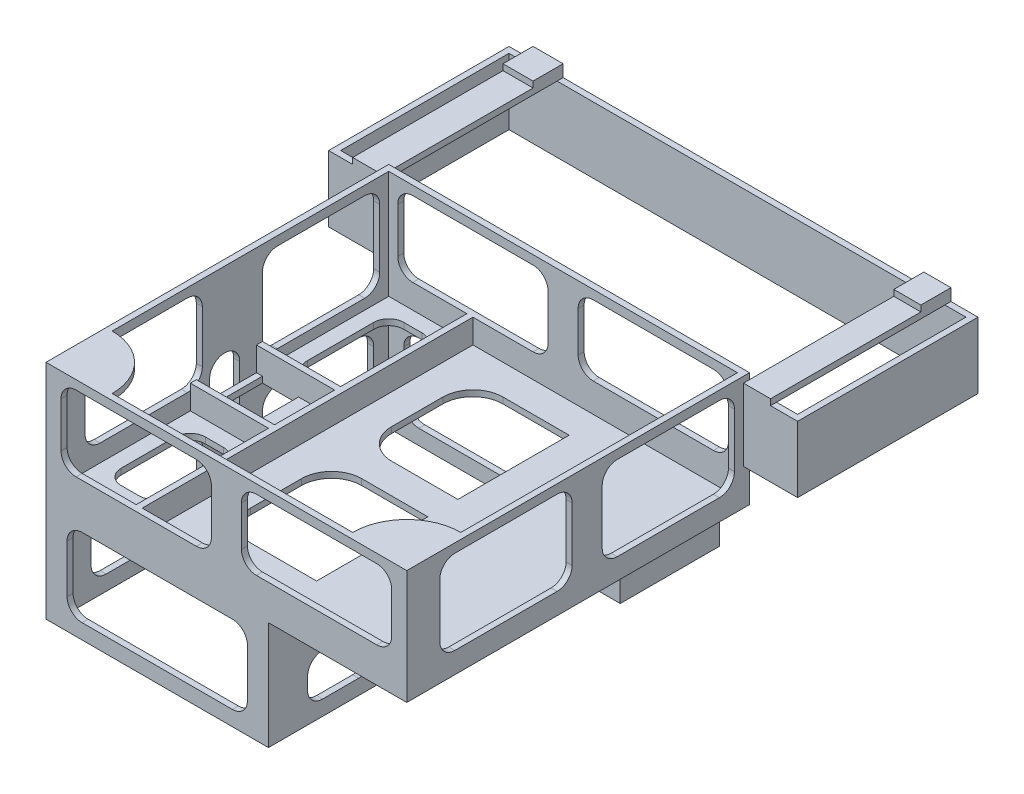
SolidWorks part; units mm, degrees
ref_plane "Front Plane" through (0, 0, 0) normal (0, 0, 1) x (1, 0, 0)
ref_plane "Top Plane" through (0, 0, 0) normal (0, 1, 0) x (1, 0, 0)
ref_plane "Right Plane" through (0, 0, 0) normal (1, 0, 0) x (0, 0, -1)
sketch "Sketch1" plane through (0, 0, 0) normal (0, 1, 0) x (1, 0, 0)
  line L1 (-113.8745, -60.9464) -> (-53.8745, -60.9464)
  line L2 (-113.8745, -60.9464) -> (-113.8745, -6.9464)
  line L3 (-113.8745, -6.9464) -> (-53.8745, -6.9464)
  line L4 (-53.8745, -60.9464) -> (-53.8745, -6.9464)
  dimension "D1" = 60
  dimension "D2" = 54
extrude "Boss-Extrude1" add sketch "Sketch1" along normal blind 38
sketch "Sketch2" plane through (0, 38, 0) normal (0, 1, 0) x (1, 0, 0)
  line L0 (-53.8745, -60.9464) -> (-53.8745, -6.9464) construction
  line L1 (-54.8745, -7.9464) -> (-98.8745, -7.9464)
  line L2 (-54.8745, -7.9464) -> (-54.8745, -59.9464)
  line L3 (-54.8745, -59.9464) -> (-98.8745, -59.9464)
  line L4 (-98.8745, -7.9464) -> (-98.8745, -59.9464)
  line L5 (-53.8745, -6.9464) -> (-113.8745, -6.9464) construction
  line L6 (-113.8745, -60.9464) -> (-53.8745, -60.9464) construction
  dimension "D1" = 1
  dimension "D2" = 1
  dimension "D3" = 1
  dimension "D4" = 44
extrude "Cut-Extrude1" cut sketch "Sketch2" against normal blind 19
sketch "Sketch3" plane through (0, 0, 0) normal (0, -1, 0) x (-1, 0, 0)
  line L0 (113.8745, -60.9464) -> (53.8745, -60.9464) construction
  line L1 (112.8745, -59.9464) -> (77.8745, -59.9464)
  line L2 (112.8745, -59.9464) -> (112.8745, -7.9464)
  line L3 (112.8745, -7.9464) -> (77.8745, -7.9464)
  line L4 (77.8745, -59.9464) -> (77.8745, -7.9464)
  line L5 (113.8745, -6.9464) -> (113.8745, -60.9464) construction
  line L6 (53.8745, -6.9464) -> (113.8745, -6.9464) construction
  dimension "D1" = 1
  dimension "D2" = 35
  dimension "D3" = 1
  dimension "D4" = 1
extrude "Cut-Extrude2" cut sketch "Sketch3" against normal blind 18
sketch "Sketch4" plane through (0, 18, 0) normal (0, -1, 0) x (-1, 0, 0)
  line L0 (77.8745, -59.9464) -> (112.8745, -59.9464) construction
  line L1 (111.8745, -39.9464) -> (105.8745, -39.9464)
  line L2 (111.8745, -39.9464) -> (111.8745, -29.9464)
  line L3 (111.8745, -29.9464) -> (105.8745, -29.9464)
  line L4 (105.8745, -39.9464) -> (105.8745, -29.9464)
  line L5 (112.8745, -7.9464) -> (77.8745, -7.9464) construction
  line L6 (112.8745, -59.9464) -> (112.8745, -7.9464) construction
  dimension "D1" = 20
  dimension "D2" = 22
  dimension "D3" = 1
  dimension "D4" = 6
extrude "Cut-Extrude3" cut sketch "Sketch4" against normal blind 38
sketch "Sketch5" plane through (0, 38, 0) normal (0, 1, 0) x (1, 0, 0)
  line L0 (-53.8745, -6.9464) -> (-113.8745, -6.9464) construction
  line L1 (-98.8745, -59.9464) -> (-112.8745, -59.9464)
  line L2 (-98.8745, -59.9464) -> (-98.8745, -7.9464)
  line L3 (-98.8745, -7.9464) -> (-112.8745, -7.9464)
  line L4 (-112.8745, -59.9464) -> (-112.8745, -7.9464)
  line L5 (-113.8745, -6.9464) -> (-113.8745, -60.9464) construction
  dimension "D1" = 1
  dimension "D2" = 1
extrude "Cut-Extrude5" cut sketch "Sketch5" against normal blind 15
sketch "Sketch6" plane through (0, 23, 0) normal (0, 1, 0) x (1, 0, 0)
  line L0 (-112.8745, -59.9464) -> (-98.8745, -59.9464) construction
  line L1 (-112.8745, -7.9464) -> (-99.8745, -7.9464)
  line L2 (-112.8745, -7.9464) -> (-112.8745, -59.9464)
  line L3 (-112.8745, -59.9464) -> (-99.8745, -59.9464)
  line L4 (-99.8745, -7.9464) -> (-99.8745, -59.9464)
  line L5 (-98.8745, -59.9464) -> (-98.8745, -7.9464) construction
  dimension "D1" = 1
extrude "Cut-Extrude6" cut sketch "Sketch6" against normal blind 4
sketch "Sketch8" plane through (0, 0, 0) normal (0, -1, 0) x (-1, 0, 0)
  line L0 (53.8745, -60.9464) -> (53.8745, -6.9464) construction
  line L1 (72.3745, -11.4464) -> (58.3745, -11.4464)
  line L2 (72.3745, -11.4464) -> (72.3745, -23.9464)
  line L3 (72.3745, -23.9464) -> (58.3745, -23.9464)
  line L4 (58.3745, -11.4464) -> (58.3745, -23.9464)
  line L6 (53.8745, -6.9464) -> (113.8745, -6.9464) construction
  dimension "D1" = 14
  dimension "D2" = 12.5
  dimension "D3" = 4.5
  dimension "D4" = 4.5
extrude "Cut-Extrude7" cut sketch "Sketch8" against normal blind 6
sketch "Sketch10" plane through (-72.3745, 0, 0) normal (1, 0, 0) x (0, 0, -1)
  line L0 (-11.4464, 6) -> (-11.4464, 0) construction
  line L1 (-23.9464, 6) -> (-11.4464, 6)
  line L2 (-23.9464, 6) -> (-23.9464, 1)
  line L3 (-23.9464, 1) -> (-11.4464, 1)
  line L4 (-11.4464, 6) -> (-11.4464, 1)
  line L5 (-23.9464, 0) -> (-11.4464, 0) construction
  dimension "D1" = 1
extrude "Cut-Extrude8" cut sketch "Sketch10" against normal blind 6
sketch "Sketch11" plane through (0, 0, 0) normal (0, -1, 0) x (1, 0, 0)
  line L0 (-113.8745, 60.9464) -> (-53.8745, 60.9464) construction
  line L1 (-68.3745, 50.9464) -> (-63.8745, 50.9464)
  line L2 (-68.3745, 50.9464) -> (-68.3745, 45.9464)
  line L3 (-68.3745, 45.9464) -> (-63.8745, 45.9464)
  line L4 (-63.8745, 50.9464) -> (-63.8745, 45.9464)
  line L5 (-53.8745, 60.9464) -> (-53.8745, 6.9464) construction
  dimension "D1" = 4.5
  dimension "D2" = 5
  dimension "D3" = 10
  dimension "D4" = 10
extrude "Cut-Extrude9" cut sketch "Sketch11" against normal blind 18
sketch "Sketch12" plane through (-68.3745, 0, 0) normal (1, 0, 0) x (0, 0, -1)
  line L0 (-50.9464, 18) -> (-50.9464, 0) construction
  line L1 (-45.9464, 18) -> (-50.9464, 18)
  line L2 (-45.9464, 18) -> (-45.9464, 1)
  line L3 (-45.9464, 1) -> (-50.9464, 1)
  line L4 (-50.9464, 18) -> (-50.9464, 1)
  line L5 (-50.9464, 0) -> (-45.9464, 0) construction
  dimension "D1" = 1
extrude "Cut-Extrude10" cut sketch "Sketch12" against normal blind 13
sketch "Sketch13" plane through (-113.8745, 0, 0) normal (-1, 0, 0) x (0, 0, 1)
  line L0 (35.233, 15) -> (35.233, 22) construction
  line L1 (32.733, 15) -> (32.733, 22)
  line L2 (37.733, 15) -> (37.733, 22)
  line L3 (59.9464, 18) -> (7.9464, 18) construction
  line L4 (39.9464, 19) -> (29.9464, 19) construction
  arc A0 (32.733, 15) -> (37.733, 15) centre (35.233, 15) ccw
  arc A1 (37.733, 22) -> (32.733, 22) centre (35.233, 22) ccw
  point P2 (35.233, 18.5)
  dimension "D1" = 3
  dimension "D2" = 3
  dimension "D3" = 2.5
extrude "Cut-Extrude11" cut sketch "Sketch13" against normal blind 1
sketch "Sketch14" plane through (0, 19, 0) normal (0, 1, 0) x (1, 0, 0)
  line L0 (-99.8745, -59.9464) -> (-99.8745, -7.9464) construction
  line L1 (-112.8745, -40.9464) -> (-99.8745, -40.9464)
  line L2 (-112.8745, -40.9464) -> (-112.8745, -39.9464)
  line L3 (-112.8745, -39.9464) -> (-99.8745, -39.9464)
  line L4 (-99.8745, -40.9464) -> (-99.8745, -39.9464)
  line L5 (-112.8745, -37.733) -> (-112.8745, -59.9464) construction
  line L6 (-105.8745, -39.9464) -> (-111.8745, -39.9464) construction
  dimension "D1" = 0
  dimension "D2" = 1
  dimension "D3" = 0
extrude "Boss-Extrude2" add sketch "Sketch14" along normal blind 4
sketch "Sketch15" plane through (0, 19, 0) normal (0, 1, 0) x (1, 0, 0)
  line L0 (-112.8745, -7.9464) -> (-112.8745, -32.733) construction
  line L1 (-112.8745, -29.9464) -> (-99.8745, -29.9464)
  line L2 (-112.8745, -29.9464) -> (-112.8745, -28.9464)
  line L3 (-112.8745, -28.9464) -> (-99.8745, -28.9464)
  line L4 (-99.8745, -29.9464) -> (-99.8745, -28.9464)
  line L5 (-99.8745, -39.9464) -> (-99.8745, -7.9464) construction
  line L6 (-111.8745, -29.9464) -> (-105.8745, -29.9464) construction
  dimension "D1" = 0
  dimension "D2" = 1
extrude "Boss-Extrude3" add sketch "Sketch15" along normal blind 4
sketch "Sketch16" plane through (0, 19, 0) normal (0, 1, 0) x (1, 0, 0)
  line L0 (-98.8745, -59.9464) -> (-54.8745, -59.9464) construction
  line L1 (-64.8745, -54.9464) -> (-88.8745, -54.9464)
  line L2 (-59.8745, -49.9464) -> (-59.8745, -41.4464)
  line L3 (-64.8745, -36.4464) -> (-88.8745, -36.4464)
  line L4 (-93.8745, -49.9464) -> (-93.8745, -41.4464)
  line L5 (-88.8745, -31.4464) -> (-64.8745, -31.4464)
  line L6 (-93.8745, -26.4464) -> (-93.8745, -17.9464)
  line L7 (-88.8745, -12.9464) -> (-64.8745, -12.9464)
  line L8 (-59.8745, -26.4464) -> (-59.8745, -17.9464)
  line L9 (-54.8745, -59.9464) -> (-54.8745, -7.9464) construction
  line L10 (-98.8745, -7.9464) -> (-98.8745, -59.9464) construction
  line L11 (-54.8745, -7.9464) -> (-98.8745, -7.9464) construction
  arc A0 (-64.8745, -31.4464) -> (-59.8745, -26.4464) centre (-64.8745, -26.4464) ccw
  arc A1 (-64.8745, -12.9464) -> (-59.8745, -17.9464) centre (-64.8745, -17.9464) cw
  arc A2 (-93.8745, -17.9464) -> (-88.8745, -12.9464) centre (-88.8745, -17.9464) cw
  arc A3 (-88.8745, -31.4464) -> (-93.8745, -26.4464) centre (-88.8745, -26.4464) cw
  arc A4 (-88.8745, -54.9464) -> (-93.8745, -49.9464) centre (-88.8745, -49.9464) cw
  arc A5 (-88.8745, -36.4464) -> (-93.8745, -41.4464) centre (-88.8745, -41.4464) ccw
  arc A6 (-59.8745, -41.4464) -> (-64.8745, -36.4464) centre (-64.8745, -41.4464) ccw
  arc A7 (-64.8745, -54.9464) -> (-59.8745, -49.9464) centre (-64.8745, -49.9464) ccw
  point P22 (-93.8745, -12.9464)
  point P25 (-93.8745, -31.4464)
  dimension "D9" = 5
  dimension "D1" = 5
  dimension "D2" = 5
  dimension "D3" = 5
  dimension "D4" = 5
  dimension "D5" = 5
  dimension "D6" = 5
  dimension "D7" = 5
  dimension "D8" = 18.5
extrude "Cut-Extrude12" cut sketch "Sketch16" against normal blind 1
sketch "Sketch17" plane through (0, 19, 0) normal (0, 1, 0) x (1, 0, 0)
  line L0 (-112.8745, -40.9464) -> (-112.8745, -59.9464) construction
  line L1 (-104.8745, -57.4464) -> (-107.8745, -57.4464)
  line L2 (-102.3745, -54.9464) -> (-102.3745, -45.9464)
  line L3 (-104.8745, -43.4464) -> (-107.8745, -43.4464)
  line L4 (-110.3745, -54.9464) -> (-110.3745, -45.9464)
  line L5 (-104.8745, -26.4464) -> (-107.8745, -26.4464)
  line L6 (-102.3745, -23.9464) -> (-102.3745, -12.9464)
  line L7 (-104.8745, -10.4464) -> (-107.8745, -10.4464)
  line L8 (-110.3745, -23.9464) -> (-110.3745, -12.9464)
  line L9 (-99.8745, -59.9464) -> (-99.8745, -40.9464) construction
  line L10 (-112.8745, -40.9464) -> (-99.8745, -40.9464) construction
  line L11 (-112.8745, -59.9464) -> (-99.8745, -59.9464) construction
  line L12 (-99.8745, -28.9464) -> (-112.8745, -28.9464) construction
  line L13 (-112.8745, -7.9464) -> (-112.8745, -28.9464) construction
  line L14 (-99.8745, -28.9464) -> (-99.8745, -7.9464) construction
  line L15 (-99.8745, -7.9464) -> (-112.8745, -7.9464) construction
  arc A0 (-102.3745, -12.9464) -> (-104.8745, -10.4464) centre (-104.8745, -12.9464) ccw
  arc A1 (-107.8745, -10.4464) -> (-110.3745, -12.9464) centre (-107.8745, -12.9464) ccw
  arc A2 (-107.8745, -26.4464) -> (-110.3745, -23.9464) centre (-107.8745, -23.9464) cw
  arc A3 (-104.8745, -26.4464) -> (-102.3745, -23.9464) centre (-104.8745, -23.9464) ccw
  arc A4 (-102.3745, -45.9464) -> (-104.8745, -43.4464) centre (-104.8745, -45.9464) ccw
  arc A5 (-107.8745, -43.4464) -> (-110.3745, -45.9464) centre (-107.8745, -45.9464) ccw
  arc A6 (-107.8745, -57.4464) -> (-110.3745, -54.9464) centre (-107.8745, -54.9464) cw
  arc A7 (-104.8745, -57.4464) -> (-102.3745, -54.9464) centre (-104.8745, -54.9464) ccw
  dimension "D9" = 2.5
  dimension "D1" = 2.5
  dimension "D2" = 2.5
  dimension "D3" = 2.5
  dimension "D4" = 2.5
  dimension "D5" = 2.5
  dimension "D6" = 2.5
  dimension "D7" = 2.5
  dimension "D8" = 2.5
extrude "Cut-Extrude13" cut sketch "Sketch17" against normal blind 1
sketch "Sketch18" plane through (-53.8745, 0, 0) normal (1, 0, 0) x (0, 0, -1)
  line L0 (-60.9464, 38) -> (-6.9464, 38) construction
  line L1 (-55.9464, 35.5) -> (-38.9464, 35.5)
  line L2 (-58.4464, 33) -> (-58.4464, 24)
  line L3 (-55.9464, 21.5) -> (-38.9464, 21.5)
  line L4 (-36.4464, 33) -> (-36.4464, 24)
  line L5 (-28.9464, 35.5) -> (-11.9464, 35.5)
  line L6 (-31.4464, 33) -> (-31.4464, 24)
  line L7 (-28.9464, 21.5) -> (-11.9464, 21.5)
  line L8 (-9.4464, 33) -> (-9.4464, 24)
  line L9 (-60.9464, 38) -> (-60.9464, 0) construction
  line L10 (-6.9464, 38) -> (-6.9464, 0) construction
  line L11 (-59.9464, 19) -> (-7.9464, 19) construction
  arc A0 (-31.4464, 24) -> (-28.9464, 21.5) centre (-28.9464, 24) ccw
  arc A1 (-11.9464, 21.5) -> (-9.4464, 24) centre (-11.9464, 24) ccw
  arc A2 (-11.9464, 35.5) -> (-9.4464, 33) centre (-11.9464, 33) cw
  arc A3 (-28.9464, 35.5) -> (-31.4464, 33) centre (-28.9464, 33) ccw
  arc A4 (-58.4464, 24) -> (-55.9464, 21.5) centre (-55.9464, 24) ccw
  arc A5 (-38.9464, 21.5) -> (-36.4464, 24) centre (-38.9464, 24) ccw
  arc A6 (-38.9464, 35.5) -> (-36.4464, 33) centre (-38.9464, 33) cw
  arc A7 (-55.9464, 35.5) -> (-58.4464, 33) centre (-55.9464, 33) ccw
  point P26 (-58.4464, 21.5)
  point P29 (-36.4464, 21.5)
  dimension "D9" = 2.5
  dimension "D1" = 2.5
  dimension "D2" = 2.5
  dimension "D3" = 2.5
  dimension "D4" = 2.5
  dimension "D5" = 5
  dimension "D6" = 22
  dimension "D7" = 2.5
  dimension "D8" = 2.5
extrude "Cut-Extrude14" cut sketch "Sketch18" against normal blind 1
sketch "Sketch19" plane through (0, 0, 6.9464) normal (0, 0, -1) x (-1, 0, 0)
  line L0 (53.8745, 38) -> (113.8745, 38) construction
  line L1 (58.8745, 35.5) -> (78.8745, 35.5)
  line L2 (56.3745, 33) -> (56.3745, 26.3041)
  line L3 (58.8745, 23.8041) -> (78.8745, 23.8041)
  line L4 (81.3745, 33) -> (81.3745, 26.3041)
  line L5 (88.8745, 35.5) -> (108.8745, 35.5)
  line L6 (86.3745, 33) -> (86.3745, 25.5)
  line L7 (88.8745, 23) -> (108.8745, 23)
  line L8 (111.3745, 33) -> (111.3745, 25.5)
  line L9 (113.8745, 38) -> (113.8745, 0) construction
  line L10 (53.8745, 38) -> (53.8745, 0) construction
  arc A0 (108.8745, 23) -> (111.3745, 25.5) centre (108.8745, 25.5) ccw
  arc A1 (108.8745, 35.5) -> (111.3745, 33) centre (108.8745, 33) cw
  arc A2 (88.8745, 35.5) -> (86.3745, 33) centre (88.8745, 33) ccw
  arc A3 (86.3745, 25.5) -> (88.8745, 23) centre (88.8745, 25.5) ccw
  arc A4 (78.8745, 23.8041) -> (81.3745, 26.3041) centre (78.8745, 26.3041) ccw
  arc A5 (78.8745, 35.5) -> (81.3745, 33) centre (78.8745, 33) cw
  arc A6 (56.3745, 26.3041) -> (58.8745, 23.8041) centre (58.8745, 26.3041) ccw
  arc A7 (58.8745, 35.5) -> (56.3745, 33) centre (58.8745, 33) ccw
  point P17 (111.3745, 23)
  point P24 (86.3745, 23)
  dimension "D8" = 2.5
  dimension "D1" = 2.5
  dimension "D2" = 2.5
  dimension "D3" = 2.5
  dimension "D4" = 2.5
  dimension "D5" = 5
  dimension "D6" = 25
  dimension "D7" = 0
extrude "Cut-Extrude15" cut sketch "Sketch19" against normal blind 60
sketch "Sketch20" plane through (-113.8745, 0, 0) normal (-1, 0, 0) x (0, 0, 1)
  line L0 (59.9464, 38) -> (7.9464, 38) construction
  line L1 (11.9464, 35.5) -> (26.4464, 35.5)
  line L2 (9.4464, 33) -> (9.4464, 23.222)
  line L3 (11.9464, 20.722) -> (26.4464, 20.722)
  line L4 (28.9464, 33) -> (28.9464, 23.222)
  line L5 (41.4464, 35.5) -> (55.9464, 35.5)
  line L6 (38.9464, 33) -> (38.9464, 24.3756)
  line L7 (41.4464, 21.8756) -> (55.9464, 21.8756)
  line L8 (58.4464, 33) -> (58.4464, 24.3756)
  line L9 (6.9464, 38) -> (6.9464, 0) construction
  line L10 (60.9464, 38) -> (60.9464, 0) construction
  line L11 (6.9464, 38) -> (60.9464, 38) construction
  arc A0 (38.9464, 24.3756) -> (41.4464, 21.8756) centre (41.4464, 24.3756) ccw
  arc A1 (55.9464, 21.8756) -> (58.4464, 24.3756) centre (55.9464, 24.3756) ccw
  arc A2 (55.9464, 35.5) -> (58.4464, 33) centre (55.9464, 33) cw
  arc A3 (41.4464, 35.5) -> (38.9464, 33) centre (41.4464, 33) ccw
  arc A4 (9.4464, 23.222) -> (11.9464, 20.722) centre (11.9464, 23.222) ccw
  arc A5 (26.4464, 20.722) -> (28.9464, 23.222) centre (26.4464, 23.222) ccw
  arc A6 (26.4464, 35.5) -> (28.9464, 33) centre (26.4464, 33) cw
  arc A7 (11.9464, 35.5) -> (9.4464, 33) centre (11.9464, 33) ccw
  point P18 (38.9464, 21.8756)
  point P21 (58.4464, 21.8756)
  dimension "D7" = 2.5
  dimension "D1" = 2.5
  dimension "D2" = 2.5
  dimension "D3" = 10
  dimension "D4" = 2.5
  dimension "D5" = 2.5
  dimension "D6" = 19.5
extrude "Cut-Extrude16" cut sketch "Sketch20" against normal blind 1
sketch "Sketch21" plane through (0, 0, 59.9464) normal (0, 0, -1) x (-1, 0, 0)
  line L0 (77.8745, 0) -> (112.8745, 0) construction
  line L1 (107.8745, 2.5) -> (82.8745, 2.5)
  line L2 (110.3745, 5) -> (110.3745, 13)
  line L3 (107.8745, 15.5) -> (82.8745, 15.5)
  line L4 (80.3745, 5) -> (80.3745, 13)
  line L5 (77.8745, 18) -> (77.8745, 0) construction
  line L6 (112.8745, 18) -> (112.8745, 0) construction
  line L7 (77.8745, 18) -> (112.8745, 18) construction
  arc A0 (110.3745, 13) -> (107.8745, 15.5) centre (107.8745, 13) ccw
  arc A1 (82.8745, 15.5) -> (80.3745, 13) centre (82.8745, 13) ccw
  arc A2 (82.8745, 2.5) -> (80.3745, 5) centre (82.8745, 5) cw
  arc A3 (107.8745, 2.5) -> (110.3745, 5) centre (107.8745, 5) ccw
  dimension "D5" = 2.5
  dimension "D1" = 2.5
  dimension "D2" = 2.5
  dimension "D3" = 2.5
  dimension "D4" = 2.5
extrude "Cut-Extrude17" cut sketch "Sketch21" along normal blind 89 and the other way blind 10
sketch "Sketch22" plane through (-112.8745, 0, 0) normal (1, 0, 0) x (0, 0, -1)
  line L0 (-59.9464, 0) -> (-7.9464, 0) construction
  line L1 (-12.9464, 2.5) -> (-26.4464, 2.5)
  line L2 (-10.4464, 5) -> (-10.4464, 13)
  line L3 (-12.9464, 15.5) -> (-26.4464, 15.5)
  line L4 (-28.9464, 5) -> (-28.9464, 13)
  line L5 (-41.4464, 2.5) -> (-54.9464, 2.5)
  line L6 (-38.9464, 5) -> (-38.9464, 13)
  line L7 (-41.4464, 15.5) -> (-54.9464, 15.5)
  line L8 (-57.4464, 5) -> (-57.4464, 13)
  line L9 (-7.9464, 18) -> (-7.9464, 0) construction
  line L10 (-32.733, 18) -> (-7.9464, 18) construction
  line L11 (-59.9464, 18) -> (-37.733, 18) construction
  line L12 (-59.9464, 18) -> (-59.9464, 0) construction
  arc A0 (-38.9464, 13) -> (-41.4464, 15.5) centre (-41.4464, 13) ccw
  arc A1 (-54.9464, 15.5) -> (-57.4464, 13) centre (-54.9464, 13) ccw
  arc A2 (-54.9464, 2.5) -> (-57.4464, 5) centre (-54.9464, 5) cw
  arc A3 (-41.4464, 2.5) -> (-38.9464, 5) centre (-41.4464, 5) ccw
  arc A4 (-26.4464, 2.5) -> (-28.9464, 5) centre (-26.4464, 5) cw
  arc A5 (-26.4464, 15.5) -> (-28.9464, 13) centre (-26.4464, 13) ccw
  arc A6 (-10.4464, 13) -> (-12.9464, 15.5) centre (-12.9464, 13) ccw
  arc A7 (-12.9464, 2.5) -> (-10.4464, 5) centre (-12.9464, 5) ccw
  point P30 (-28.9464, 15.5)
  point P33 (-10.4464, 15.5)
  dimension "D9" = 2.5
  dimension "D1" = 2.5
  dimension "D2" = 10
  dimension "D3" = 2.5
  dimension "D4" = 2.5
  dimension "D5" = 2.5
  dimension "D6" = 2.5
  dimension "D7" = 2.5
  dimension "D8" = 18.5
extrude "Cut-Extrude18" cut sketch "Sketch22" against normal blind 10
sketch "Sketch23" plane through (0, 38, 0) normal (0, 1, 0) x (1, 0, 0)
  line L1 (-112.8745, -59.9464) -> (-54.8745, -59.9464)
  line L2 (-112.8745, -59.9464) -> (-112.8745, -7.9464)
  line L3 (-112.8745, -7.9464) -> (-54.8745, -7.9464)
  line L4 (-54.8745, -59.9464) -> (-54.8745, -7.9464)
extrude "Boss-Extrude4" add sketch "Sketch23" against normal blind 1
sketch "Sketch24" plane through (0, 38, 0) normal (0, 1, 0) x (1, 0, 0)
  line L0 (-113.8745, -6.9464) -> (-113.8745, -60.9464) construction
  line L1 (-113.8745, -50.9464) -> (-53.8745, -50.9464)
  line L2 (-113.8745, -50.9464) -> (-113.8745, -16.9464)
  line L3 (-113.8745, -16.9464) -> (-53.8745, -16.9464)
  line L4 (-53.8745, -50.9464) -> (-53.8745, -16.9464)
  line L5 (-53.8745, -60.9464) -> (-53.8745, -6.9464) construction
  line L6 (-53.8745, -6.9464) -> (-113.8745, -6.9464) construction
  line L7 (-103.8745, -6.9464) -> (-63.8745, -6.9464)
  line L8 (-103.8745, -6.9464) -> (-103.8745, -60.9464)
  line L9 (-103.8745, -60.9464) -> (-63.8745, -60.9464)
  line L10 (-63.8745, -6.9464) -> (-63.8745, -60.9464)
  line L11 (-113.8745, -60.9464) -> (-53.8745, -60.9464) construction
  line L12 (-58.8745, -60.9464) -> (-56.3745, -60.9464) construction
  line M5 (-113.8745, -6.9464) -> (-113.8745, -60.9464)
  line M6 (-113.8745, -60.9464) -> (-53.8745, -60.9464)
  line M7 (-53.8745, -60.9464) -> (-53.8745, -6.9464)
  line M8 (-53.8745, -6.9464) -> (-113.8745, -6.9464)
  dimension "D1" = 10
  dimension "D2" = 10
  dimension "D3" = 10
  dimension "D4" = 10
extrude "Cut-Extrude20" cut sketch "Sketch24" against normal blind 1 contours L10 L1 L8 M6 | L3 L10 L1 M7 | L10 L8 L3 M8 | L10 L3 L8 L1 | L8 L3 L1 M5
fillet "Fillet1" radius 9 3 edges at (-103.8745, 37, 55.4464) (-108.3745, 37, 50.9464) (-103.8745, 37.5, 50.9464)
fillet "Fillet2" radius 9 3 edges at (-63.8745, 37, 12.4464) (-59.3745, 37, 16.9464) (-63.8745, 37.5, 16.9464)
fillet "Fillet3" radius 9 3 edges at (-63.8745, 37, 55.4464) (-63.8745, 37.5, 50.9464) (-59.3745, 37, 50.9464)
fillet "Fillet4" radius 9 3 edges at (-108.3745, 37, 16.9464) (-103.8745, 37, 12.4464) (-103.8745, 37.5, 16.9464)
sketch "Sketch27" plane through (0, 0, 6.9464) normal (0, 0, -1) x (-1, 0, 0)
  line L0 (53.8745, 38) -> (53.8745, 0) construction
  line L1 (53.8745, 24) -> (43.8745, 24)
  line L2 (53.8745, 24) -> (53.8745, 35)
  line L3 (53.8745, 35) -> (43.8745, 35)
  line L4 (43.8745, 24) -> (43.8745, 35)
  line L5 (113.8745, 38) -> (113.8745, 0) construction
  line L6 (113.8745, 24) -> (123.8745, 24)
  line L7 (113.8745, 24) -> (113.8745, 35)
  line L8 (113.8745, 35) -> (123.8745, 35)
  line L9 (123.8745, 24) -> (123.8745, 35)
  line L10 (63.8745, 37) -> (103.8745, 37) construction
  dimension "D1" = 2
  dimension "D2" = 2
  dimension "D3" = 80
  dimension "D4" = 10
  dimension "D5" = 11
  dimension "D6" = 11
extrude "Boss-Extrude10" add sketch "Sketch27" against normal blind 1
sketch "Sketch31" plane through (0, 0, 6.9464) normal (0, 0, -1) x (-1, 0, 0)
  line L0 (43.8745, 24) -> (53.8745, 24) construction
  line L1 (43.8745, 24) -> (44.8745, 24)
  line L2 (43.8745, 24) -> (43.8745, 35)
  line L3 (43.8745, 35) -> (44.8745, 35)
  line L4 (44.8745, 24) -> (44.8745, 35)
  line L5 (53.8745, 35) -> (43.8745, 35) construction
  line L6 (123.8745, 35) -> (113.8745, 35) construction
  line L7 (122.8745, 35) -> (123.8745, 35)
  line L8 (122.8745, 35) -> (122.8745, 24)
  line L9 (122.8745, 24) -> (123.8745, 24)
  line L10 (123.8745, 35) -> (123.8745, 24)
  dimension "D1" = 1
  dimension "D2" = 1
extrude "Boss-Extrude12" add sketch "Sketch31" along normal blind 29
sketch "Sketch33" plane through (-44.8745, 0, 0) normal (-1, 0, 0) x (0, 0, 1)
  line L0 (-22.0536, 24) -> (6.9464, 24) construction
  line L1 (-22.0536, 35) -> (-21.0536, 35)
  line L2 (-22.0536, 35) -> (-22.0536, 24)
  line L3 (-22.0536, 24) -> (-21.0536, 24)
  line L4 (-21.0536, 35) -> (-21.0536, 24)
  dimension "D1" = 1
extrude "Boss-Extrude13" add sketch "Sketch33" along normal blind 78
sketch "Sketch34" plane through (0, 35, 0) normal (0, 1, 0) x (1, 0, 0)
  line L0 (-123.8745, -7.9464) -> (-113.8745, -7.9464) construction
  line L1 (-123.8745, 22.0536) -> (-43.8745, 22.0536) construction
  line L2 (-118.8745, -7.9464) -> (-113.8745, -7.9464)
  line L3 (-118.8745, -7.9464) -> (-118.8745, 22.0536)
  line L4 (-118.8745, 22.0536) -> (-113.8745, 22.0536)
  line L5 (-113.8745, -7.9464) -> (-113.8745, 22.0536)
  line L7 (-53.8745, -7.9464) -> (-49.3745, -7.9464)
  line L8 (-53.8745, -7.9464) -> (-53.8745, 22.0536)
  line L9 (-53.8745, 22.0536) -> (-49.3745, 22.0536)
  line L10 (-49.3745, -7.9464) -> (-49.3745, 22.0536)
extrude "Boss-Extrude14" add sketch "Sketch34" along normal blind 1
sketch "Sketch35" plane through (-122.8745, 0, 0) normal (1, 0, 0) x (0, 0, -1)
  line L0 (21.0536, 24) -> (-6.9464, 24) construction
  line L1 (21.0536, 24) -> (-6.9464, 24)
  line L2 (21.0536, 24) -> (21.0536, 35)
  line L3 (21.0536, 35) -> (-6.9464, 35)
  line L4 (-6.9464, 24) -> (-6.9464, 35)
extrude "Boss-Extrude15" add sketch "Sketch35" along normal blind 1
sketch "Sketch37" plane through (-123.8745, 0, 0) normal (-1, 0, 0) x (0, 0, 1)
  line L1 (7.9464, 35) -> (-22.0536, 35)
  line L2 (7.9464, 35) -> (7.9464, 24)
  line L3 (7.9464, 24) -> (-22.0536, 24)
  line L4 (-22.0536, 35) -> (-22.0536, 24)
extrude "Cut-Extrude21" cut sketch "Sketch37" against normal blind 1
sketch "Sketch38" plane through (-44.8745, 0, 0) normal (-1, 0, 0) x (0, 0, 1)
  line L1 (6.9464, 35) -> (-21.0536, 35)
  line L2 (6.9464, 35) -> (6.9464, 24)
  line L3 (6.9464, 24) -> (-21.0536, 24)
  line L4 (-21.0536, 35) -> (-21.0536, 24)
extrude "Boss-Extrude16" add sketch "Sketch38" along normal blind 1
sketch "Sketch39" plane through (-43.8745, 0, 0) normal (1, 0, 0) x (0, 0, -1)
  line L1 (-7.9464, 24) -> (22.0536, 24)
  line L2 (-7.9464, 24) -> (-7.9464, 35)
  line L3 (-7.9464, 35) -> (22.0536, 35)
  line L4 (22.0536, 24) -> (22.0536, 35)
extrude "Cut-Extrude22" cut sketch "Sketch39" against normal blind 1
sketch "Sketch40" plane through (0, 0, 60.9464) normal (0, 0, 1) x (1, 0, 0)
  line L0 (-113.8745, 38) -> (-113.8745, 0) construction
  line L1 (-53.8745, 0) -> (-113.8745, 0)
  line L2 (-53.8745, 0) -> (-53.8745, 37)
  line L3 (-53.8745, 37) -> (-113.8745, 37)
  line L4 (-113.8745, 0) -> (-113.8745, 37)
  dimension "D1" = 37
extrude "Boss-Extrude17" add sketch "Sketch40" along normal blind 3
sketch "Sketch41" plane through (0, 0, 59.9464) normal (0, 0, -1) x (-1, 0, 0)
  line L1 (112.8745, 0) -> (77.8745, 0)
  line L2 (112.8745, 0) -> (112.8745, 18)
  line L3 (112.8745, 18) -> (77.8745, 18)
  line L4 (77.8745, 0) -> (77.8745, 18)
extrude "Cut-Extrude23" cut sketch "Sketch41" against normal blind 3
sketch "Sketch42" plane through (0, 0, 59.9464) normal (0, 0, -1) x (-1, 0, 0)
  line L0 (98.8745, 19) -> (54.8745, 19) construction
  line L1 (98.8745, 19) -> (54.8745, 19)
  line L2 (98.8745, 19) -> (98.8745, 37)
  line L3 (98.8745, 37) -> (54.8745, 37)
  line L4 (54.8745, 19) -> (54.8745, 37)
  line L5 (54.8745, 19) -> (54.8745, 37) construction
extrude "Cut-Extrude24" cut sketch "Sketch42" against normal blind 3
sketch "Sketch44" plane through (0, 0, 59.9464) normal (0, 0, -1) x (-1, 0, 0)
  line L0 (103.8745, 37) -> (98.8745, 37) construction
  line L1 (112.8745, 19) -> (99.8745, 19)
  line L2 (112.8745, 19) -> (112.8745, 37)
  line L3 (112.8745, 37) -> (99.8745, 37)
  line L4 (99.8745, 19) -> (99.8745, 37)
  dimension "D1" = 13
extrude "Cut-Extrude25" cut sketch "Sketch44" against normal blind 3
sketch "Sketch45" plane through (-98.8745, 0, 0) normal (1, 0, 0) x (0, 0, -1)
  line L0 (-62.9464, 37) -> (-59.9464, 37) construction
  line L1 (-62.9464, 37) -> (-59.9464, 37)
  line L2 (-62.9464, 37) -> (-62.9464, 23)
  line L3 (-62.9464, 23) -> (-59.9464, 23)
  line L4 (-59.9464, 37) -> (-59.9464, 23)
  line L5 (-60.9464, 23) -> (-7.9464, 23) construction
extrude "Cut-Extrude26" cut sketch "Sketch45" against normal blind 3
sketch "Sketch47" plane through (0, 38, 0) normal (0, 1, 0) x (1, 0, 0)
  line L1 (-113.8745, -6.9464) -> (-53.8745, -6.9464)
  line L2 (-113.8745, -6.9464) -> (-113.8745, -16.9464)
  line L3 (-113.8745, -16.9464) -> (-53.8745, -16.9464)
  line L4 (-53.8745, -6.9464) -> (-53.8745, -16.9464)
extrude "Cut-Extrude27" cut sketch "Sketch47" against normal blind 1
sketch "Sketch48" plane through (0, 38, 0) normal (0, 1, 0) x (1, 0, 0)
  line L1 (-113.8745, -60.9464) -> (-53.8745, -60.9464)
  line L2 (-113.8745, -60.9464) -> (-113.8745, -50.9464)
  line L3 (-113.8745, -50.9464) -> (-53.8745, -50.9464)
  line L4 (-53.8745, -60.9464) -> (-53.8745, -50.9464)
extrude "Cut-Extrude28" cut sketch "Sketch48" against normal blind 1
sketch "Sketch49" plane through (0, 37, 0) normal (0, 1, 0) x (1, 0, 0)
  line L0 (-53.8745, -63.9464) -> (-53.8745, -6.9464) construction
  line L1 (-113.8745, -63.9464) -> (-53.8745, -63.9464)
  line L2 (-113.8745, -63.9464) -> (-113.8745, -53.9464)
  line L3 (-113.8745, -53.9464) -> (-53.8745, -53.9464)
  line L4 (-53.8745, -63.9464) -> (-53.8745, -53.9464)
  dimension "D1" = 10
extrude "Boss-Extrude18" add sketch "Sketch49" against normal blind 1
sketch "Sketch50" plane through (0, 37, 0) normal (0, 1, 0) x (1, 0, 0)
  line L0 (-54.8745, -53.9464) -> (-112.8745, -53.9464) construction
  line L1 (-103.8745, -53.9464) -> (-63.8745, -53.9464)
  line L2 (-103.8745, -53.9464) -> (-103.8745, -62.9464)
  line L3 (-103.8745, -62.9464) -> (-63.8745, -62.9464)
  line L4 (-63.8745, -53.9464) -> (-63.8745, -62.9464)
  line L5 (-53.8745, -63.9464) -> (-113.8745, -63.9464) construction
  line L6 (-53.8745, -63.9464) -> (-53.8745, -6.9464) construction
  line L7 (-113.8745, -6.9464) -> (-113.8745, -63.9464) construction
  dimension "D1" = 1
  dimension "D2" = 10
  dimension "D3" = 10
extrude "Cut-Extrude29" cut sketch "Sketch50" against normal blind 1 contours L2 L1 L4 L3
fillet "Fillet5" radius 9 5 edges at (-108.3745, 36, 53.9464) (-108.3745, 37, 53.9464) (-103.8745, 36, 58.4464) (-103.8745, 36.5, 53.9464) (-103.8745, 37, 58.4464)
fillet "Fillet6" radius 9 5 edges at (-59.3745, 36, 53.9464) (-59.3745, 37, 53.9464) (-63.8745, 37, 58.4464) (-63.8745, 36.5, 53.9464) (-63.8745, 36, 58.4464)
sketch "Sketch51" plane through (0, 36, 0) normal (0, 1, 0) x (1, 0, 0)
  line L0 (-113.8745, 22.0536) -> (-118.8745, 22.0536) construction
  line L1 (-113.8745, 22.0536) -> (-118.8745, 22.0536)
  line L2 (-113.8745, 22.0536) -> (-113.8745, 17.0536)
  line L3 (-113.8745, 17.0536) -> (-118.8745, 17.0536)
  line L4 (-118.8745, 22.0536) -> (-118.8745, 17.0536)
  line L5 (-118.8745, 22.0536) -> (-118.8745, -7.9464) construction
  line L6 (-53.8745, 22.0536) -> (-53.8745, -6.9464) construction
  line L7 (-49.3745, 22.0536) -> (-53.8745, 22.0536)
  line L8 (-49.3745, 22.0536) -> (-49.3745, 17.0536)
  line L9 (-49.3745, 17.0536) -> (-53.8745, 17.0536)
  line L10 (-53.8745, 22.0536) -> (-53.8745, 17.0536)
  dimension "D1" = 5
extrude "Boss-Extrude19" add sketch "Sketch51" along normal blind 1
sketch "Sketch53" plane through (0, 0, 0) normal (0, -1, 0) x (-1, 0, 0)
  line L0 (53.8745, -63.9464) -> (53.8745, -6.9464) construction
  line L1 (53.8745, -34.3392) -> (76.8745, -34.3392)
  line L2 (53.8745, -34.3392) -> (53.8745, -43.9464)
  line L3 (53.8745, -43.9464) -> (76.8745, -43.9464)
  line L4 (76.8745, -34.3392) -> (76.8745, -43.9464)
  line L5 (113.8745, -63.9464) -> (53.8745, -63.9464) construction
  line L6 (53.8745, -52.9464) -> (76.8745, -52.9464)
  line L7 (53.8745, -52.9464) -> (53.8745, -63.9464)
  line L8 (53.8745, -63.9464) -> (76.8745, -63.9464)
  line L9 (76.8745, -52.9464) -> (76.8745, -63.9464)
  line L10 (77.8745, -7.9464) -> (77.8745, -62.9464) construction
  line L11 (53.8745, -43.9464) -> (61.8745, -43.9464)
  line L12 (53.8745, -43.9464) -> (53.8745, -52.9464)
  line L13 (53.8745, -52.9464) -> (61.8745, -52.9464)
  line L14 (61.8745, -43.9464) -> (61.8745, -52.9464)
  line L15 (68.3745, -45.9464) -> (63.8745, -45.9464) construction
  line L16 (63.8745, -45.9464) -> (63.8745, -50.9464) construction
  line L17 (63.8745, -50.9464) -> (68.3745, -50.9464) construction
  point P21 (63.8745, -48.4464)
  line M20 (53.8745, -6.9464) -> (53.8745, -63.9464)
  line M21 (53.8745, -63.9464) -> (113.8745, -63.9464)
  dimension "D1" = 1
  dimension "D2" = 1
  dimension "D3" = 2
  dimension "D4" = 2
  dimension "D5" = 2
extrude "Cut-Extrude30" cut sketch "Sketch53" against normal blind 18 contours L4 L1 L3 M20 | L14 L3 L6 M20 | L9 L6 M20 M21
sketch "Sketch54" plane through (0, 0, 0) normal (0, -1, 0) x (-1, 0, 0)
  line L0 (53.8745, -34.3392) -> (53.8745, -6.9464) construction
  line L1 (53.8745, -34.3392) -> (76.8745, -34.3392)
  line L2 (53.8745, -34.3392) -> (53.8745, -25.9464)
  line L3 (53.8745, -25.9464) -> (76.8745, -25.9464)
  line L4 (76.8745, -34.3392) -> (76.8745, -25.9464)
  line L5 (53.8745, -6.9464) -> (76.8745, -6.9464)
  line L6 (53.8745, -6.9464) -> (53.8745, -9.4464)
  line L7 (53.8745, -9.4464) -> (76.8745, -9.4464)
  line L8 (76.8745, -6.9464) -> (76.8745, -9.4464)
  line L9 (53.8745, -6.9464) -> (113.8745, -6.9464) construction
  line L10 (58.3745, -11.4464) -> (58.3745, -23.9464) construction
  line L11 (53.8745, -25.9464) -> (56.3745, -25.9464)
  line L12 (53.8745, -25.9464) -> (53.8745, -9.4464)
  line L13 (53.8745, -9.4464) -> (56.3745, -9.4464)
  line L14 (56.3745, -25.9464) -> (56.3745, -9.4464)
  line L15 (72.3745, -11.4464) -> (58.3745, -11.4464) construction
  line L16 (58.3745, -23.9464) -> (72.3745, -23.9464) construction
  line L17 (77.8745, -7.9464) -> (77.8745, -62.9464) construction
  line M22 (113.8745, -6.9464) -> (53.8745, -6.9464)
  line M23 (53.8745, -6.9464) -> (53.8745, -34.3392)
  line M24 (53.8745, -34.3392) -> (76.8745, -34.3392)
  dimension "D1" = 2
  dimension "D2" = 2
  dimension "D3" = 2
  dimension "D4" = 1
  dimension "D5" = 1
extrude "Cut-Extrude31" cut sketch "Sketch54" against normal blind 18 contours L4 L3 M24 M23 | L3 L14 L7 M23 | L8 L7 M22 M23
sketch "Sketch55" plane through (0, 19, 0) normal (0, 1, 0) x (1, 0, 0)
  line L0 (-77.8745, -12.9464) -> (-77.8745, -31.4464) construction
  line L1 (-77.8745, -57.7928) -> (-58.5121, -57.7928)
  line L2 (-77.8745, -57.7928) -> (-77.8745, -10.6433)
  line L3 (-77.8745, -10.6433) -> (-58.5121, -10.6433)
  line L4 (-58.5121, -57.7928) -> (-58.5121, -10.6433)
  dimension "D1" = 0
extrude "Boss-Extrude20" add sketch "Sketch55" against normal blind 1
sketch "Sketch57" plane through (0, 0, 0) normal (0, -1, 0) x (-1, 0, 0)
  line L1 (76.8745, -52.9464) -> (61.8745, -52.9464)
  line L2 (76.8745, -52.9464) -> (76.8745, -43.9464)
  line L3 (76.8745, -43.9464) -> (61.8745, -43.9464)
  line L4 (61.8745, -52.9464) -> (61.8745, -43.9464)
  point P4 (62.9872, -42.6074)
  point P5 (74.312, -48.3712)
  point P8 (83.9332, -49.8642)
extrude "Cut-Extrude32" cut sketch "Sketch57" against normal blind 15
sketch "Sketch58" plane through (-76.8745, 0, 0) normal (1, 0, 0) x (0, 0, -1)
  line L0 (-45.9464, 15) -> (-43.9464, 15) construction
  line L1 (-51.2363, 0.5985) -> (-44.9464, 0.5985)
  line L2 (-51.2363, 0.5985) -> (-51.2363, 15)
  line L3 (-51.2363, 15) -> (-44.9464, 15)
  line L4 (-44.9464, 0.5985) -> (-44.9464, 15)
  point P6 (-43.8493, 2.5399)
extrude "Boss-Extrude21" add sketch "Sketch58" against normal blind 1
sketch "Sketch59" plane through (0, 15, 0) normal (0, -1, 0) x (-1, 0, 0)
  line L1 (76.8745, -52.9464) -> (61.8745, -52.9464)
  line L2 (76.8745, -52.9464) -> (76.8745, -43.9464)
  line L3 (76.8745, -43.9464) -> (61.8745, -43.9464)
  line L4 (61.8745, -52.9464) -> (61.8745, -43.9464)
  point P4 (62.2491, -43.7306)
  point P5 (67.4306, -45.7722)
extrude "Boss-Extrude26" add sketch "Sketch59" along normal blind 1
sketch "Sketch60" plane through (0, 14, 0) normal (0, -1, 0) x (-1, 0, 0)
  line L0 (61.8745, -52.9464) -> (76.8745, -52.9464) construction
  line L1 (68.3745, -50.9464) -> (63.8745, -50.9464)
  line L2 (68.3745, -50.9464) -> (68.3745, -45.9464)
  line L3 (68.3745, -45.9464) -> (63.8745, -45.9464)
  line L4 (63.8745, -50.9464) -> (63.8745, -45.9464)
  line L5 (61.8745, -43.9464) -> (61.8745, -52.9464) construction
  line L6 (76.8745, -43.9464) -> (61.8745, -43.9464) construction
  point P4 (64.047, -46.4113)
  dimension "D1" = 2
  dimension "D2" = 2
  dimension "D3" = 4.5
  dimension "D4" = 2
extrude "Cut-Extrude33" cut sketch "Sketch60" against normal blind 1
sketch "Sketch61" plane through (0, 0, 0) normal (0, -1, 0) x (-1, 0, 0)
  line L1 (58.3745, -23.9464) -> (72.3745, -23.9464)
  line L2 (58.3745, -23.9464) -> (58.3745, -11.4464)
  line L3 (58.3745, -11.4464) -> (72.3745, -11.4464)
  line L4 (72.3745, -23.9464) -> (72.3745, -11.4464)
  point P4 (71.7541, -11.8205)
extrude "Cut-Extrude34" cut sketch "Sketch61" against normal blind 18
sketch "Sketch62" plane through (-77.8745, 0, 0) normal (-1, 0, 0) x (0, 0, 1)
  line L0 (23.9464, 6) -> (23.9464, 1) construction
  line L1 (23.9464, 18) -> (11.4464, 18)
  line L2 (23.9464, 18) -> (23.9464, 13)
  line L3 (23.9464, 13) -> (11.4464, 13)
  line L4 (11.4464, 18) -> (11.4464, 13)
  line L5 (11.4464, 1) -> (11.4464, 6) construction
  line L6 (7.9464, 18) -> (12.9464, 18) construction
  point P4 (16.2954, 12.9914)
  dimension "D1" = 0
  dimension "D2" = 0
  dimension "D3" = 0
  dimension "D4" = 5
extrude "Cut-Extrude35" cut sketch "Sketch62" against normal blind 18
sketch "Sketch63" plane through (0, 0, 0) normal (0, -1, 0) x (1, 0, 0)
  line L0 (-56.3745, 9.4464) -> (-76.8745, 9.4464) construction
  line L1 (-56.3745, 25.9464) -> (-76.8745, 25.9464)
  line L2 (-56.3745, 25.9464) -> (-56.3745, 9.4464)
  line L3 (-56.3745, 9.4464) -> (-76.8745, 9.4464)
  line L4 (-76.8745, 25.9464) -> (-76.8745, 9.4464)
  line L5 (-56.3745, 9.4464) -> (-76.8745, 9.4464) construction
extrude "Cut-Extrude36" cut sketch "Sketch63" against normal blind 12
sketch "Sketch64" plane through (-76.8745, 0, 0) normal (1, 0, 0) x (0, 0, -1)
  line L1 (-24.3075, 0.7139) -> (-10.7319, 0.7139)
  line L2 (-24.3075, 0.7139) -> (-24.3075, 7.4343)
  line L3 (-24.3075, 7.4343) -> (-10.7319, 7.4343)
  line L4 (-10.7319, 0.7139) -> (-10.7319, 7.4343)
extrude "Boss-Extrude27" add sketch "Sketch64" against normal blind 1
sketch "Sketch65" plane through (0, 0, 63.9464) normal (0, 0, 1) x (1, 0, 0)
  line L0 (-108.8745, 35.5) -> (-88.8745, 35.5) construction
  line L1 (-108.8745, 35.5) -> (-88.8745, 35.5)
  line L2 (-111.3745, 33) -> (-111.3745, 25.5)
  line L3 (-108.8745, 23) -> (-88.8745, 23)
  line L4 (-86.3745, 33) -> (-86.3745, 25.5)
  line L5 (-78.8745, 35.5) -> (-58.8745, 35.5)
  line L6 (-81.3745, 33) -> (-81.3745, 26.3041)
  line L7 (-78.8745, 23.8041) -> (-58.8745, 23.8041)
  line L8 (-56.3745, 33) -> (-56.3745, 26.3041)
  line L9 (-78.8745, 35.5) -> (-58.8745, 35.5) construction
  line L10 (-56.3745, 33) -> (-56.3745, 26.3041) construction
  line L11 (-111.3745, 25.5) -> (-111.3745, 33) construction
  line L12 (-86.3745, 33) -> (-86.3745, 25.5) construction
  line L13 (-81.3745, 26.3041) -> (-81.3745, 33) construction
  line L14 (-58.8745, 23.8041) -> (-78.8745, 23.8041) construction
  line L15 (-88.8745, 23) -> (-98.8745, 23) construction
  arc A0 (-111.3745, 25.5) -> (-108.8745, 23) centre (-108.8745, 25.5) ccw
  arc A1 (-108.8745, 35.5) -> (-111.3745, 33) centre (-108.8745, 33) ccw
  arc A2 (-58.8745, 35.5) -> (-56.3745, 33) centre (-58.8745, 33) cw
  arc A3 (-58.8745, 23.8041) -> (-56.3745, 26.3041) centre (-58.8745, 26.3041) ccw
  arc A4 (-81.3745, 26.3041) -> (-78.8745, 23.8041) centre (-78.8745, 26.3041) ccw
  arc A5 (-78.8745, 35.5) -> (-81.3745, 33) centre (-78.8745, 33) ccw
  arc A6 (-88.8745, 23) -> (-86.3745, 25.5) centre (-88.8745, 25.5) ccw
  arc A7 (-88.8745, 35.5) -> (-86.3745, 33) centre (-88.8745, 33) cw
  dimension "D9" = 2.5
  dimension "D10" = 2.5
  dimension "D1" = 0
  dimension "D2" = 0
  dimension "D3" = 0
  dimension "D4" = 0
  dimension "D5" = 0
  dimension "D6" = 0
  dimension "D7" = 0
  dimension "D8" = 0
extrude "Cut-Extrude37" cut sketch "Sketch65" against normal blind 1
sketch "Sketch66" plane through (0, 0, 63.9464) normal (0, 0, 1) x (1, 0, 0)
  line L0 (-82.8745, 2.5) -> (-107.8745, 2.5) construction
  line L1 (-107.8745, 15.5) -> (-82.8745, 15.5)
  line L2 (-110.3745, 13) -> (-110.3745, 5)
  line L3 (-107.8745, 2.5) -> (-82.8745, 2.5)
  line L4 (-80.3745, 13) -> (-80.3745, 5)
  line L5 (-110.3745, 5) -> (-110.3745, 13) construction
  line L6 (-80.3745, 13) -> (-80.3745, 5) construction
  line L7 (-107.8745, 15.5) -> (-82.8745, 15.5) construction
  arc A0 (-110.3745, 5) -> (-107.8745, 2.5) centre (-107.8745, 5) ccw
  arc A1 (-82.8745, 2.5) -> (-80.3745, 5) centre (-82.8745, 5) ccw
  arc A2 (-82.8745, 15.5) -> (-80.3745, 13) centre (-82.8745, 13) cw
  arc A3 (-107.8745, 15.5) -> (-110.3745, 13) centre (-107.8745, 13) ccw
  dimension "D5" = 2.5
  dimension "D1" = 0
  dimension "D2" = 0
  dimension "D3" = 0
  dimension "D4" = 0
extrude "Cut-Extrude38" cut sketch "Sketch66" against normal blind 1
sketch "Sketch67" plane through (-76.8745, 0, 0) normal (1, 0, 0) x (0, 0, -1)
  line L0 (-54.9464, 2.5) -> (-41.4464, 2.5) construction
  line L1 (-38.9464, 2.5) -> (-28.9464, 2.5)
  line L2 (-41.4464, 5) -> (-41.4464, 13)
  line L3 (-38.9464, 15.5) -> (-28.9464, 15.5)
  line L4 (-26.4464, 5) -> (-26.4464, 13)
  line L5 (-18.9464, 2.5) -> (-12.9464, 2.5)
  line L6 (-21.4464, 5) -> (-21.4464, 7)
  line L7 (-18.9464, 9.5) -> (-12.9464, 9.5)
  line L8 (-10.4464, 5) -> (-10.4464, 7)
  line L9 (-54.9464, 2.5) -> (-48.9464, 2.5)
  line L10 (-57.4464, 5) -> (-57.4464, 7)
  line L11 (-54.9464, 9.5) -> (-48.9464, 9.5)
  line L12 (-46.4464, 5) -> (-46.4464, 7)
  line L13 (-26.4464, 2.5) -> (-12.9464, 2.5) construction
  line L14 (-25.9464, 12) -> (-9.4464, 12) construction
  line L15 (-25.9464, 18) -> (-43.9464, 18) construction
  line L16 (-10.4464, 5) -> (-10.4464, 13) construction
  line L17 (-57.4464, 13) -> (-57.4464, 5) construction
  arc A0 (-21.4464, 7) -> (-18.9464, 9.5) centre (-18.9464, 7) cw
  arc A1 (-18.9464, 2.5) -> (-21.4464, 5) centre (-18.9464, 5) cw
  arc A2 (-12.9464, 2.5) -> (-10.4464, 5) centre (-12.9464, 5) ccw
  arc A3 (-12.9464, 9.5) -> (-10.4464, 7) centre (-12.9464, 7) cw
  arc A4 (-41.4464, 13) -> (-38.9464, 15.5) centre (-38.9464, 13) cw
  arc A5 (-28.9464, 15.5) -> (-26.4464, 13) centre (-28.9464, 13) cw
  arc A6 (-28.9464, 2.5) -> (-26.4464, 5) centre (-28.9464, 5) ccw
  arc A7 (-38.9464, 2.5) -> (-41.4464, 5) centre (-38.9464, 5) cw
  arc A8 (-48.9464, 2.5) -> (-46.4464, 5) centre (-48.9464, 5) ccw
  arc A9 (-48.9464, 9.5) -> (-46.4464, 7) centre (-48.9464, 7) cw
  arc A10 (-57.4464, 7) -> (-54.9464, 9.5) centre (-54.9464, 7) cw
  arc A11 (-54.9464, 2.5) -> (-57.4464, 5) centre (-54.9464, 5) cw
  point P28 (-21.4464, 2.5)
  point P31 (-10.4464, 2.5)
  point P36 (-41.4464, 15.5)
  point P39 (-26.4464, 15.5)
  dimension "D13" = 2.5
  dimension "D1" = 0
  dimension "D2" = 0
  dimension "D3" = 0
  dimension "D4" = 5
  dimension "D5" = 5
  dimension "D6" = 2.5
  dimension "D7" = 2.5
  dimension "D8" = 2.5
  dimension "D9" = 15
  dimension "D10" = 0
  dimension "D11" = 0
  dimension "D12" = 11
extrude "Cut-Extrude39" cut sketch "Sketch67" against normal blind 1
